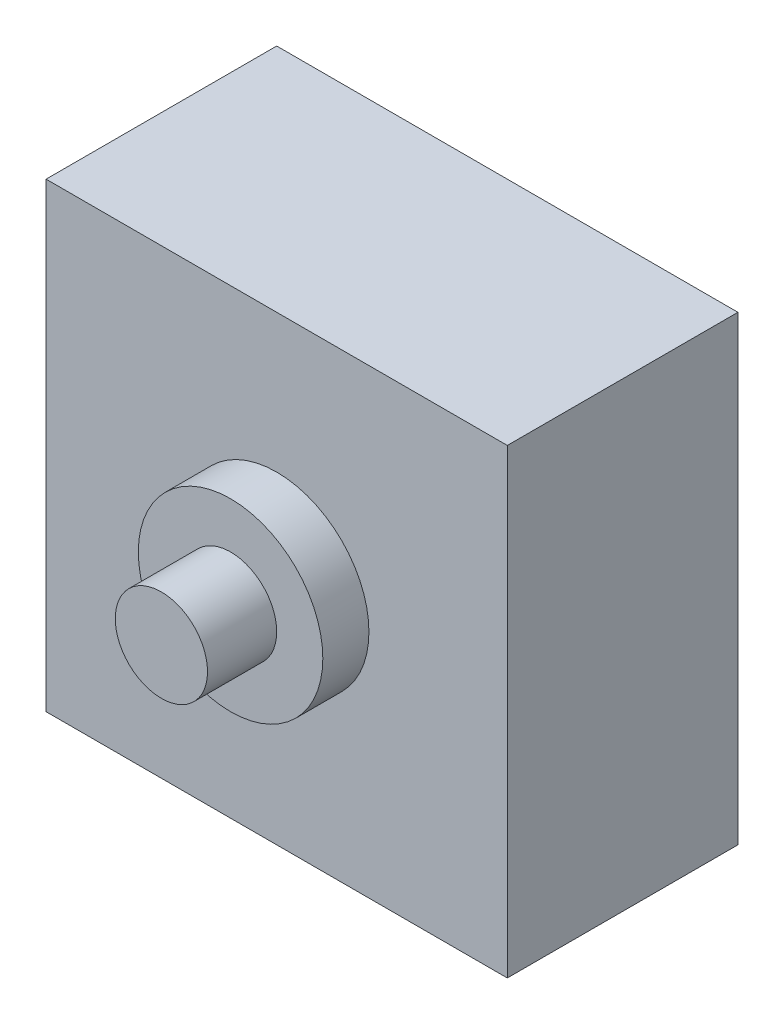
SolidWorks part; units mm, degrees
ref_plane "前视基准面" through (0, 0, 0) normal (0, 0, 1) x (1, 0, 0)
ref_plane "上视基准面" through (0, 0, 0) normal (0, 1, 0) x (1, 0, 0)
ref_plane "右视基准面" through (0, 0, 0) normal (1, 0, 0) x (0, 0, -1)
other "Configuration Table"
sketch "Sketch1" plane through (0, 0, 0) normal (0, 0, 1) x (1, 0, 0)
  line L1 (-100, -100) -> (100, -100)
  line L2 (-100, -100) -> (-100, 100)
  line L3 (-100, 100) -> (100, 100)
  line L4 (100, -100) -> (100, 100)
  line L5 (-100, -100) -> (100, 100) construction
  line L6 (-100, 100) -> (100, -100) construction
  point P0 (0, 0)
extrude "Boss-Extrude1" add sketch "Sketch1" along normal blind 100
ref_plane "Plane1" through (0, 0, 100) normal (0, 0, 1) x (1, 0, 0)
sketch "Sketch2" plane through (0, 0, 100) normal (0, 0, 1) x (1, 0, 0)
  circle A0 centre (0, 0) radius 40
extrude "Boss-Extrude2" add sketch "Sketch2" along normal blind 20
ref_plane "Plane2" through (0, 0, 120) normal (0, 0, 1) x (1, 0, 0)
sketch "Sketch3" plane through (0, 0, 120) normal (0, 0, 1) x (1, 0, 0)
  circle A0 centre (0, 0) radius 20
extrude "Boss-Extrude3" add sketch "Sketch3" along normal blind 30
ref_plane "mount_face_bottom" through (0, 0, 0) normal (0, 0, 1) x (1, 0, 0)
ref_plane "boss_top_face" through (0, 0, 150) normal (0, 0, 1) x (1, 0, 0)
sketch3d "3DSketch1"
  line L0 (0, 0, 0) -> (0, 0, 1000) construction
ref_axis "main_axis_z" through (0, 0, 0) along (0, 0, 1)
